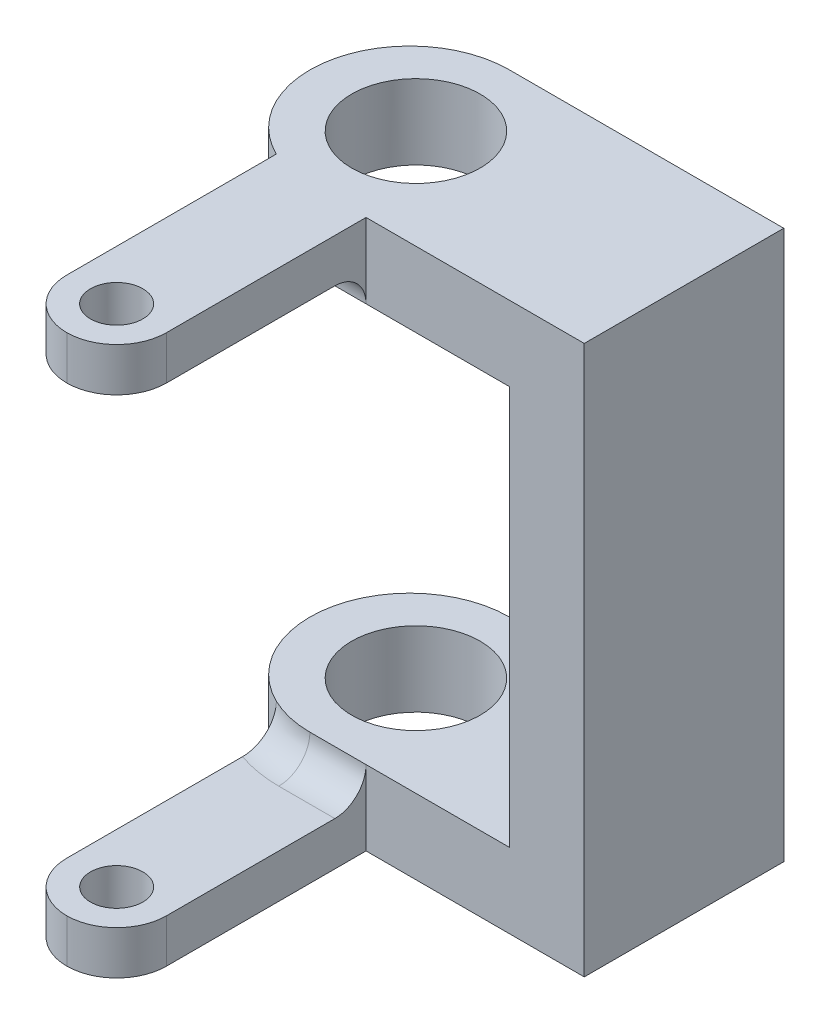
SolidWorks part; units mm, degrees
ref_plane "Front Plane" through (0, 0, 0) normal (0, 0, 1) x (1, 0, 0)
ref_plane "Top Plane" through (0, 0, 0) normal (0, 1, 0) x (1, 0, 0)
ref_plane "Right Plane" through (0, 0, 0) normal (1, 0, 0) x (0, 0, -1)
sketch "Sketch1" plane through (0, 0, 0) normal (0, 1, 0) x (1, 0, 0)
  line L1 (-1.5, -4) -> (1.5, -4)
  line L2 (-1.5, -4) -> (-1.5, 4)
  line L3 (-1.5, 4) -> (1.5, 4)
  line L4 (1.5, -4) -> (1.5, 4)
  line L5 (-1.5, -4) -> (1.5, 4) construction
  line L6 (-1.5, 4) -> (1.5, -4) construction
  point P0 (0, 0)
  dimension "D1" = 3
  dimension "D2" = 8
extrude "Boss-Extrude1" add sketch "Sketch1" along normal blind 8
sketch "Sketch2" plane through (0, 8, 0) normal (0, 1, 0) x (1, 0, 0)
  line L0 (1.5, -4) -> (1.5, 4) construction
  line L1 (1.5, -4) -> (1.5, 4)
  line L2 (1.5, -4) -> (-13.5, -4)
  line L3 (-13.5, -4) -> (-13.5, 4)
  line L4 (-13.5, 4) -> (1.5, 4)
  dimension "D1" = 15
extrude "Boss-Extrude2" add sketch "Sketch2" along normal blind 3
sketch "Sketch3" plane through (0, 11, 0) normal (0, 1, 0) x (1, 0, 0)
  line L0 (-13.5, 0) -> (-9.25, 0) construction
  line L1 (-13.5, 4) -> (-13.5, -4) construction
  circle A0 centre (-9.25, 0) radius 2.575
  point P6 (-11.825, 0)
  dimension "D1" = 5.15
  dimension "D2" = 4.25
extrude "Cut-Extrude1" cut sketch "Sketch3" against normal up to surface (3 mm away) up to face at (-7.5, 8, 0)
fillet "Fillet1" radius 4 2 edges at (-13.5, 9.5, 4) (-13.5, 9.5, -4)
sketch "Sketch4" plane through (0, 0, 4) normal (0, 0, 1) x (1, 0, 0)
  line L0 (-6.675, 11) -> (-11.825, 11) construction
  line L1 (-6.675, 11) -> (-11.825, 11) construction
  line L3 (-11.25, 9.25) -> (-7.25, 9.25)
  line L4 (-11.25, 9.25) -> (-11.25, 11)
  line L5 (-11.25, 11) -> (-7.25, 11)
  line L6 (-7.25, 9.25) -> (-7.25, 11)
  line L7 (-11.25, 9.25) -> (-7.25, 11) construction
  line L8 (-11.25, 11) -> (-7.25, 9.25) construction
  line L11 (-9.25, 11) -> (-9.25, 10.125) construction
  point P2 (-9.25, 10.125)
  dimension "D1" = 4
  dimension "D2" = 1.75
extrude "Boss-Extrude3" add sketch "Sketch4" along normal blind 10 and the other way up to surface other way up to face at (-11.9142, 9.5, 2.4142)
sketch "Sketch5" plane through (0, 11, 0) normal (0, 1, 0) x (1, 0, 0)
  line L0 (-7.25, -14) -> (-11.25, -14) construction
  circle A0 centre (-9.25, -12) radius 1.05
  dimension "D1" = 2.1
  dimension "D2" = 2
extrude "Cut-Extrude2" cut sketch "Sketch5" against normal up to surface (3 mm away) up to face at (-9.25, 8, -2.575)
fillet "Fillet2" radius 2 2 edges at (-11.25, 10.125, 14) (-7.25, 10.125, 14)
fillet "Fillet3" radius 1.25 2 edges at (-8.375, 9.25, 4) (-10.3979, 9.25, 3.8979)
mirror "Mirror1" about plane through (0, 0, 0) normal (0, 1, 0) of "Fillet3", "Fillet2", "Cut-Extrude2", "Cut-Extrude1", "Boss-Extrude2", "Boss-Extrude1", "Fillet1", "Boss-Extrude3"
